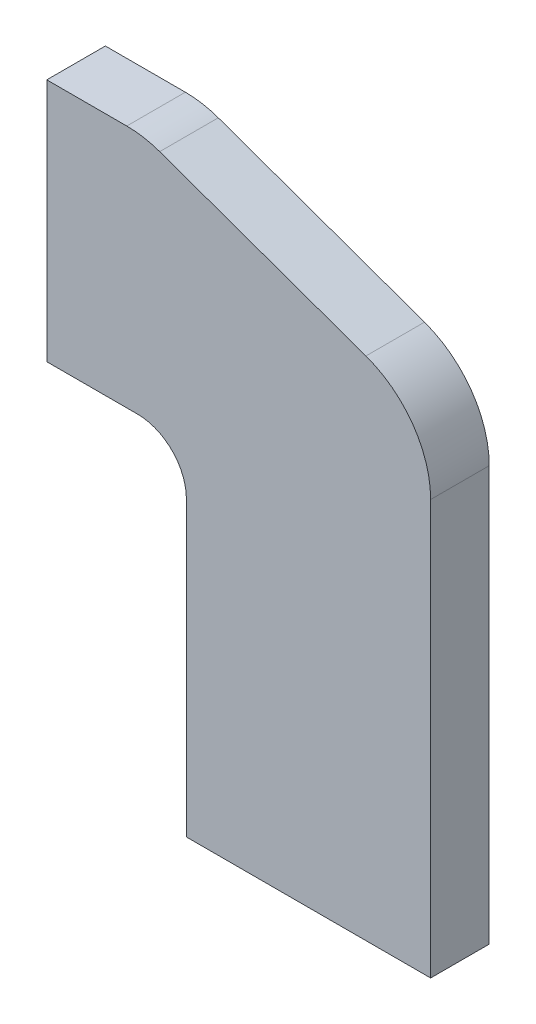
SolidWorks part; units mm, degrees
ref_plane "Спереди" through (0, 0, 0) normal (0, 0, 1) x (1, 0, 0)
ref_plane "Сверху" through (0, 0, 0) normal (0, 1, 0) x (1, 0, 0)
ref_plane "Справа" through (0, 0, 0) normal (1, 0, 0) x (0, 0, -1)
sketch "Эскиз1" plane through (0, 0, 0) normal (0, 0, 1) x (1, 0, 0)
  line L1 (0, 0) -> (78.62, 0)
  line L2 (0, 0) -> (0, 50)
  line L3 (0, 50) -> (78.62, 50)
  line L4 (78.62, 0) -> (78.62, 50)
  dimension "D1" = 78.62
  dimension "D2" = 50
extrude "Бобышка-Вытянуть1" add sketch "Эскиз1" along normal blind 12
sketch "Эскиз3" plane through (0, 0, 12) normal (0, 0, 1) x (1, 0, 0)
  line L0 (19.8589, 50) -> (78.62, 28.9521)
  line L5 (78.62, 0) -> (28.5958, 0)
  line L6 (78.62, 0) -> (78.62, 10)
  line L7 (78.62, 10) -> (28.5958, 10)
  line L8 (28.5958, 0) -> (28.5958, 10)
  line L9 (78.62, 50) -> (0, 50) construction
  line L10 (78.62, 0) -> (78.62, 50) construction
  line L11 (78.62, 28.9521) -> (78.62, 50)
  line L12 (78.62, 50) -> (19.8589, 50)
  dimension "D1" = 50.0242
  dimension "D2" = 10
extrude "Вырез-Вытянуть1" cut sketch "Эскиз3" against normal through all
fillet "Скругление3" radius 20 1 edges at (78.62, 28.9521, 6)
fillet "Скругление4" radius 20 1 edges at (19.8589, 50, 6)
sketch "Эскиз5" plane through (0, 0, 0) normal (-1, 0, 0) x (0, 0, 1)
  line L1 (0, 50) -> (0, 0) construction
  line L2 (12, 0) -> (0, 0) construction
  line L3 (12, 50) -> (0, 50) construction
  circle A0 centre (6, 7) radius 2.5
  circle A1 centre (6, 41) radius 2.5
  dimension "D1" = 5
  dimension "D2" = 6
  dimension "D3" = 34
  dimension "D4" = 7
  dimension "D5" = 9
extrude "Вырез-Вытянуть3" cut sketch "Эскиз5" against normal blind 20
sketch "Эскиз6" plane through (0, 0, 12) normal (0, 0, 1) x (1, 0, 0)
  line L1 (28.5958, 10) -> (78.62, 10)
  line L2 (28.5958, 10) -> (28.5958, -70)
  line L3 (28.5958, -70) -> (78.62, -70)
  line L4 (78.62, 10) -> (78.62, -70)
  point P5 (78.62, 10)
  dimension "D1" = 80
extrude "Бобышка-Вытянуть2" add sketch "Эскиз6" against normal up to surface (12 mm away) up to face at (35.8158, 24.4211, 0)
fillet "Скругление5" radius 10 1 edges at (28.5958, 0, 6)
sketch "Эскиз7" plane through (0, -70, 0) normal (0, -1, 0) x (1, 0, 0)
  line L0 (28.5958, 0) -> (28.5958, 12) construction
  circle A0 centre (38.5958, 6) radius 2.5
  circle A1 centre (68.5958, 6) radius 2.5
  point P4 (28.5958, 6)
  dimension "D1" = 5
  dimension "D2" = 0
  dimension "D3" = 10
  dimension "D4" = 2
extrude "Вырез-Вытянуть4" cut sketch "Эскиз7" against normal blind 30
